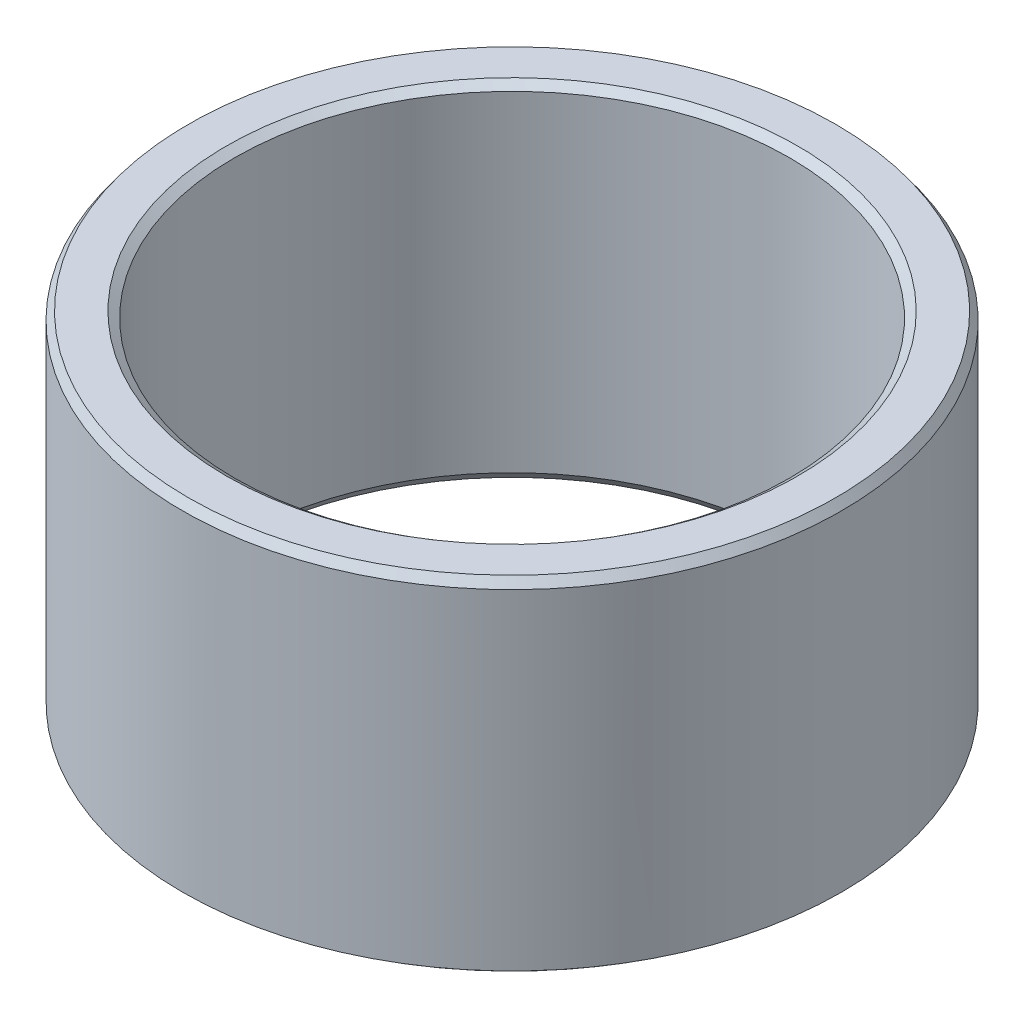
SolidWorks part; units mm, degrees
ref_plane "Front Plane" through (0, 0, 0) normal (0, 0, 1) x (1, 0, 0)
ref_plane "Top Plane" through (0, 0, 0) normal (0, 1, 0) x (1, 0, 0)
ref_plane "Right Plane" through (0, 0, 0) normal (1, 0, 0) x (0, 0, -1)
sketch "Sketch1" plane through (0, 0, 0) normal (0, 1, 0) x (1, 0, 0)
  circle A0 centre (0, 0) radius 22.5
  dimension "SLEEVE_OD" = 45
extrude "Boss-Extrude1" add sketch "Sketch1" along normal blind 23.5216
sketch "Sketch2" plane through (0, 0, 0) normal (0, 1, 0) x (1, 0, 0)
  circle A0 centre (0, 0) radius 18.9461
  dimension "BORE_D" = 37.8922
extrude "Cut-Extrude1" cut sketch "Sketch2" along normal through all
chamfer "Chamfer1" distance 0.5653 angle 35.917 4 edges at (0, 23.5216, 18.9461) (0, 0, 18.9461) (0, 0, 22.5) (0, 23.5216, 22.5) first distance on face at (0, 23.5216, 18.9461) first distance on face at (0, 0, 18.9461) first distance on face at (0, 23.5216, 22.5)
